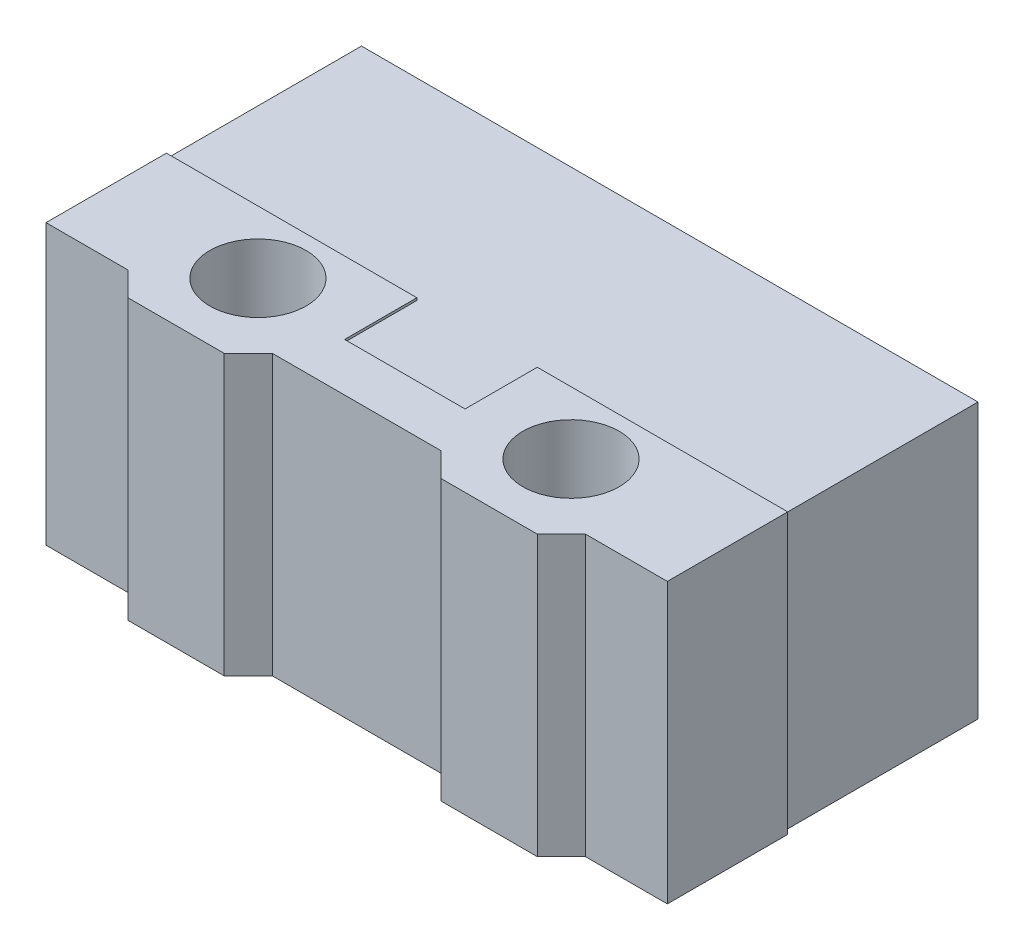
SolidWorks part; units mm, degrees
material "PBT General Purpose"
ref_plane "Front Plane" through (0, 0, 0) normal (0, 0, 1) x (1, 0, 0)
ref_plane "Top Plane" through (0, 0, 0) normal (0, 1, 0) x (1, 0, 0)
ref_plane "Right Plane" through (0, 0, 0) normal (1, 0, 0) x (0, 0, -1)
sketch "Sketch1" plane through (0, 0, 0) normal (0, 1, 0) x (1, 0, 0)
  line L0 (9.7519, 16.7311) -> (22.5519, 16.7311) construction
  line L5 (-6.4, -0.75) -> (-1.25, -0.75)
  line L6 (-6.4, 3.25) -> (6.4, 3.25)
  line L7 (-6.4, 3.25) -> (-6.4, -3.25)
  line L8 (-6.4, -3.25) -> (6.4, -3.25)
  line L9 (6.4, 3.25) -> (6.4, -3.25)
  line L10 (-6.4, 3.25) -> (6.4, -3.25) construction
  line L11 (-6.4, -3.25) -> (6.4, 3.25) construction
  line L12 (-1.25, -0.75) -> (-1.25, -2.25)
  line L13 (-1.25, -2.25) -> (1.25, -2.25)
  line L14 (1.25, -2.25) -> (1.25, -0.75)
  line L15 (1.25, -0.75) -> (6.4, -0.75)
  line L16 (-3.25, -2.05) -> (-6.4, -2.05) construction
  line L21 (3.25, -2.05) -> (6.4, -2.05) construction
  line L22 (-4.75, -3.25) -> (-4.25, -3.75)
  line L23 (-4.25, -3.75) -> (-2.25, -3.75)
  line L24 (-2.25, -3.75) -> (-1.75, -3.25)
  line L25 (1.75, -3.25) -> (2.25, -3.75)
  line L26 (2.25, -3.75) -> (4.25, -3.75)
  line L27 (4.25, -3.75) -> (4.75, -3.25)
  line L28 (6.4, -0.75) -> (6.45, -0.75)
  line L29 (6.45, -0.75) -> (6.45, -3.25)
  line L30 (6.45, -3.25) -> (6.4, -3.25)
  line L31 (-6.4, -0.75) -> (-6.45, -0.75)
  line L32 (-6.45, -0.75) -> (-6.45, -3.25)
  line L33 (-6.45, -3.25) -> (-6.4, -3.25)
  point P2 (0, 0)
  point P19 (-3.25, -2.05)
  point P20 (3.25, -2.05)
  point P36 (3.25, -3.75)
  point P37 (-3.25, -3.75)
  dimension "D1" = 12.8
  dimension "D2" = 12.8
  dimension "D3" = 6.5
  dimension "D4" = 2.5
  dimension "D5" = 6.5
  dimension "D6" = 4
  dimension "D7" = 1.2
  dimension "D8" = 2
  dimension "D9" = 0.5
  dimension "D10" = 1.5
  dimension "D11" = 0.05
  dimension "D12" = 0.05
extrude "Boss-Extrude1" add sketch "Sketch1" along normal mid plane 5.7 contours L14 L15 L9 L6 L7 L5 L12 L13 region at (0, 0, -1.0623)
extrude "Boss-Extrude2" add sketch "Sketch1<3>" along normal mid plane 5.8 contours L30 L29 L28 L9 | L15 L14 L13 L12 L5 L7 L8 L9 | L26 L27 L8 L25 | L23 L24 L8 L22 | L32 L33 L7 L31 region at (-3.825, 0, 0.8804) region at (-6.425, 0, 2) region at (-3.25, 0, 3.4833) region at (6.425, 0, 2) region at (3.25, 0, 3.4833)
sketch "Sketch1<3>" plane through (0, 0, 0) normal (0, 1, 0) x (1, 0, 0) same geometry as "Sketch1"
hole_wizard "Ø2.0mm Dowel Hole1" positions "Sketch5" profile "Sketch6" hole size "Ø2.0" standard "ISO" end condition through all
sketch "Sketch5" plane through (0, -2.9, 0) normal (0, -1, 0) x (-1, 0, 0)
  point P0 (3.25, -2.05)
  point P3 (-3.25, -2.05)
sketch "Sketch6" plane through (-3.25, -2.9, 2.05) normal (1, 0, 0) x (0, 0, -1)
  line L0 (0, 0) -> (0, 5.8)
  line L1 (0, 5.8) -> (1, 5.8)
  line L2 (1, 5.8) -> (1, 0)
  line L5 (1, 0) -> (0, 0)
  line L11 (0, -6.35) -> (0, 107.95) construction
  dimension "Thru Hole Dia." = 2
  dimension "Thru Hole Depth" = 5.8
